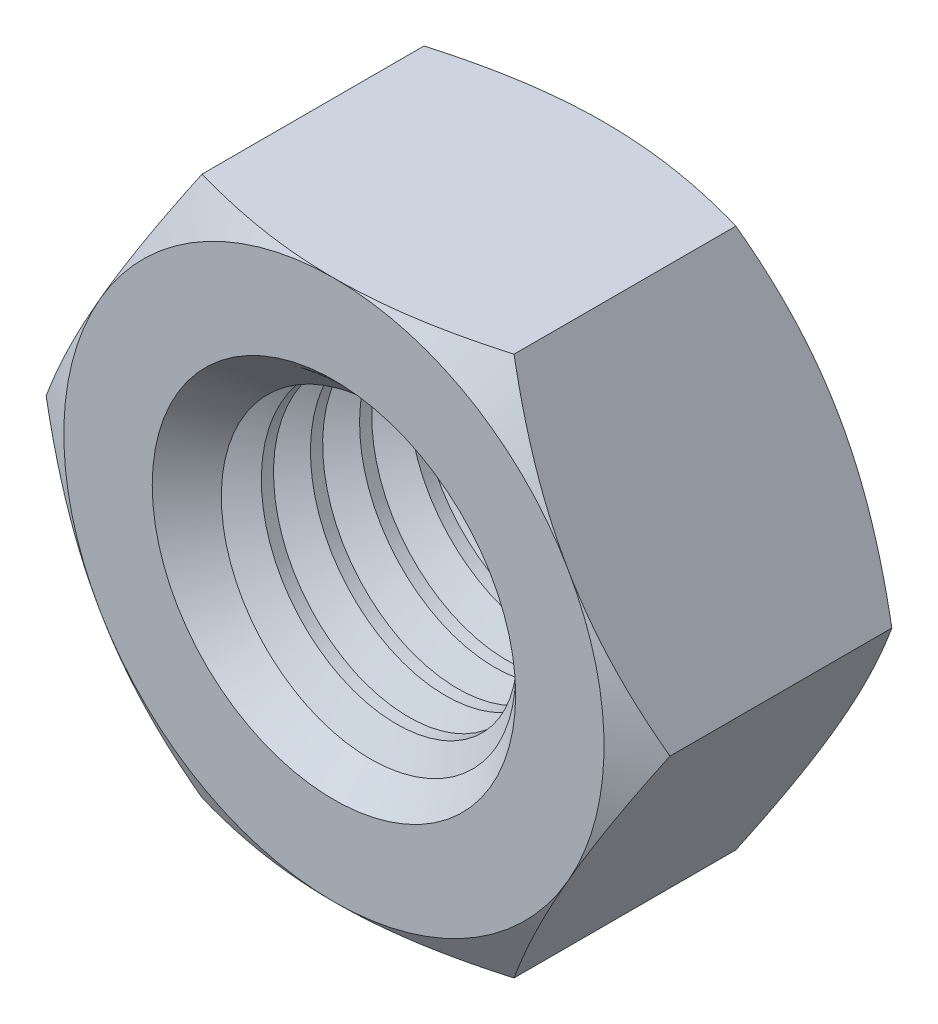
SolidWorks part; units mm, degrees
ref_plane "Front" through (0, 0, 0) normal (0, 0, 1) x (1, 0, 0)
ref_plane "Top" through (0, 0, 0) normal (0, 1, 0) x (1, 0, 0)
ref_plane "Right" through (0, 0, 0) normal (1, 0, 0) x (0, 0, -1)
sketch "Çizim1" plane through (0, 0, 0) normal (0, 0, 1) x (1, 0, 0)
  line L1 (6.3509, 0) -> (3.1754, 5.5)
  line L2 (3.1754, 5.5) -> (-3.1754, 5.5)
  line L3 (-3.1754, 5.5) -> (-6.3509, 0)
  line L4 (-6.3509, 0) -> (-3.1754, -5.5)
  line L5 (-3.1754, -5.5) -> (3.1754, -5.5)
  line L6 (3.1754, -5.5) -> (6.3509, 0)
  circle A0 centre (0, 0) radius 5.5 construction
  point P1 (0, 0)
  dimension "D1" = 11
extrude "Yükseklik-Ekstrüzyon1" add sketch "Çizim1" along normal blind 5.5
sketch "Çizim2" plane through (0, 0, 5.5) normal (0, 0, 1) x (1, 0, 0)
  circle A0 centre (0, 0) radius 5.5
extrude "Kes-Ekstrüzyon1" cut sketch "Çizim2" against normal blind 5.5 draft 60 flip side to cut
sketch "Çizim3" plane through (0, 0, 0) normal (0, 0, -1) x (-1, 0, 0)
  circle A0 centre (0, 0) radius 5.5
extrude "Kes-Ekstrüzyon2" cut sketch "Çizim3" against normal blind 5.5 draft 60 flip side to cut
sketch "Çizim4" plane through (0, 0, 0) normal (0, 0, -1) x (-1, 0, 0)
  circle A0 centre (0, 0) radius 2.85
  dimension "D1" = 5.7
extrude "Kes-Ekstrüzyon3" cut sketch "Çizim4" against normal blind 5.5
chamfer "Pah1" distance 0.85 angle 45 2 edges at (-2.85, 0, 5.5) (-2.85, 0, 0)
sketch "Çizim5" plane through (0, 0, 0) normal (0, 0, -1) x (-1, 0, 0)
  circle A0 centre (0, 0) radius 2.85
curve "Helis/Spiral1" pitch 1 height 7 radius 2.85 centre (0, 0, 0) axis (0, 0, 1) start towards (1, 0, 0)
ref_plane "Düzlem1" through (2.85, 0, 7) normal (0, 0.9984, 0.0558) x (1, 0, 0)
sketch "Çizim6" plane through (2.85, 0, 7) normal (0, 0.9984, 0.0558) x (1, 0, 0)
  line L1 (0.65, 0) -> (-0.1898, 0.4849)
  line L3 (-0.1898, -0.4849) -> (0.65, 0)
  line L4 (-0.1898, 0.4849) -> (-0.1898, -0.4849)
  line L5 (-0.325, 0.5629) -> (-0.325, 0) [skipped]
  circle A0 centre (0, 0) radius 0.325 construction
  dimension "D1" = 0.65
sweep "Kes-Süpür1" cut profiles "Çizim6" path "Helis/Spiral1" align with end faces yes
